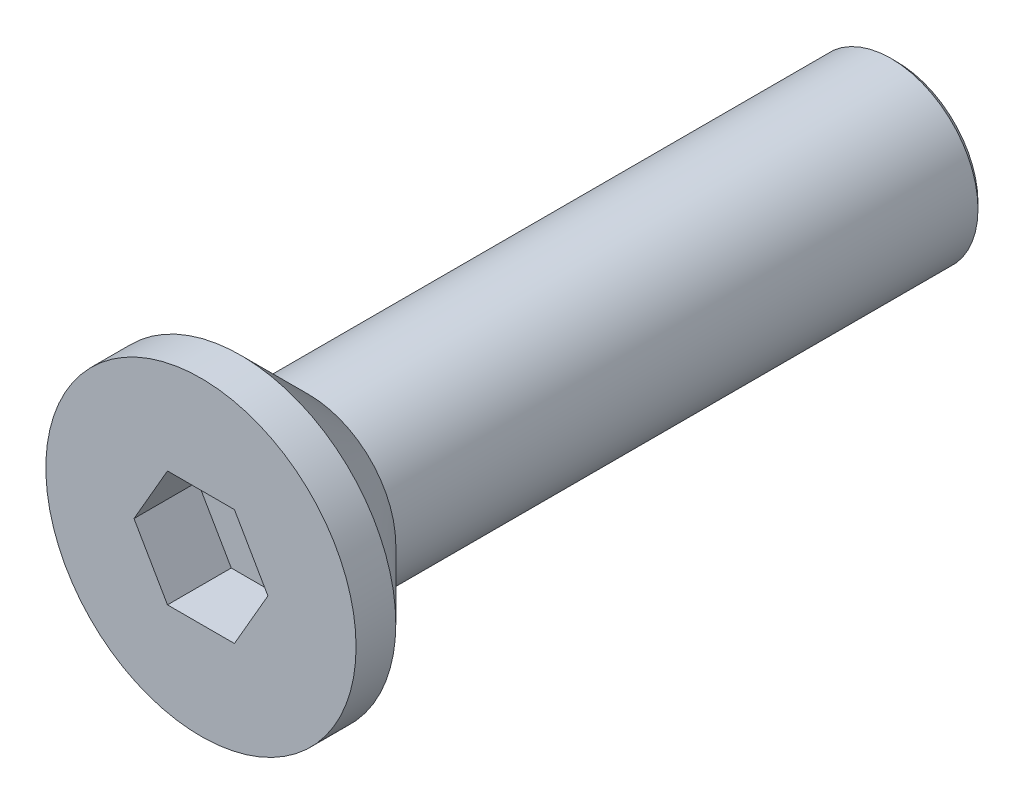
SolidWorks part; units mm, degrees
material "ALLOY STEEL, ASTM A 574M"
ref_plane "Front" through (0, 0, 0) normal (0, 0, 1) x (1, 0, 0)
ref_plane "Top" through (0, 0, 0) normal (0, 1, 0) x (1, 0, 0)
ref_plane "Side" through (0, 0, 0) normal (1, 0, 0) x (0, 0, -1)
ref_axis "Axis1" through (0, 0, 50) along (0, 0, -1)
sketch "Body_Sketch" plane through (0, 0, 0) normal (1, 0, 0) x (0, 0, -1)
  line L0 (0, 0) -> (88.7451, 0) construction
  line L1 (0, 1.5) -> (10.04, 1.5)
  line L2 (10.14, 1.4) -> (10.14, 0)
  line L3 (10.14, 0) -> (-1.86, 0)
  line L4 (-1.86, 0) -> (-1.86, 2.675)
  line L5 (-1.86, 2.675) -> (-1.175, 2.675)
  line L6 (-1.175, 2.675) -> (0, 1.5)
  line L7 (0, 0) -> (0, 1.5) construction
  line L8 (10.04, 1.5) -> (10.14, 1.4)
  line L9 (-1.86, 2.675) -> (-1.86, 3.36) construction
  line L10 (-1.175, 2.675) -> (-1.86, 3.36) construction
  point P4 (10.14, 1.5)
  dimension "Body_Dia" = 3
  dimension "Point_Chamfer" = 0.1
  dimension "D3" = 45
  dimension "D4" = 45
  dimension "Head_Dia_Min" = 5.35
  dimension "Head_Dia_Sharp" = 6.72
  dimension "Body_Length" = 12
revolve "Body_Revolve" add sketch "Body_Sketch" angle 360 about L0
sketch "Key_Sketch" plane through (0, 0, 1.86) normal (0, 0, 1) x (1, 0, 0)
  line L0 (0, 0) -> (1.1547, 0) construction
  line L1 (1.1547, 0) -> (0.5774, 1)
  line L2 (0.5774, 1) -> (-0.5774, 1)
  line L3 (-0.5774, 1) -> (-1.1547, 0)
  line L4 (-1.1547, 0) -> (-0.5774, -1)
  line L5 (-0.5774, -1) -> (0.5774, -1)
  line L6 (0.5774, -1) -> (1.1547, 0)
  circle A0 centre (0, 0) radius 1 construction
  dimension "Hex_Size" = 2
extrude "Hex_Cut" cut sketch "Key_Sketch" against normal blind 1.1
other "PropertyManager"
